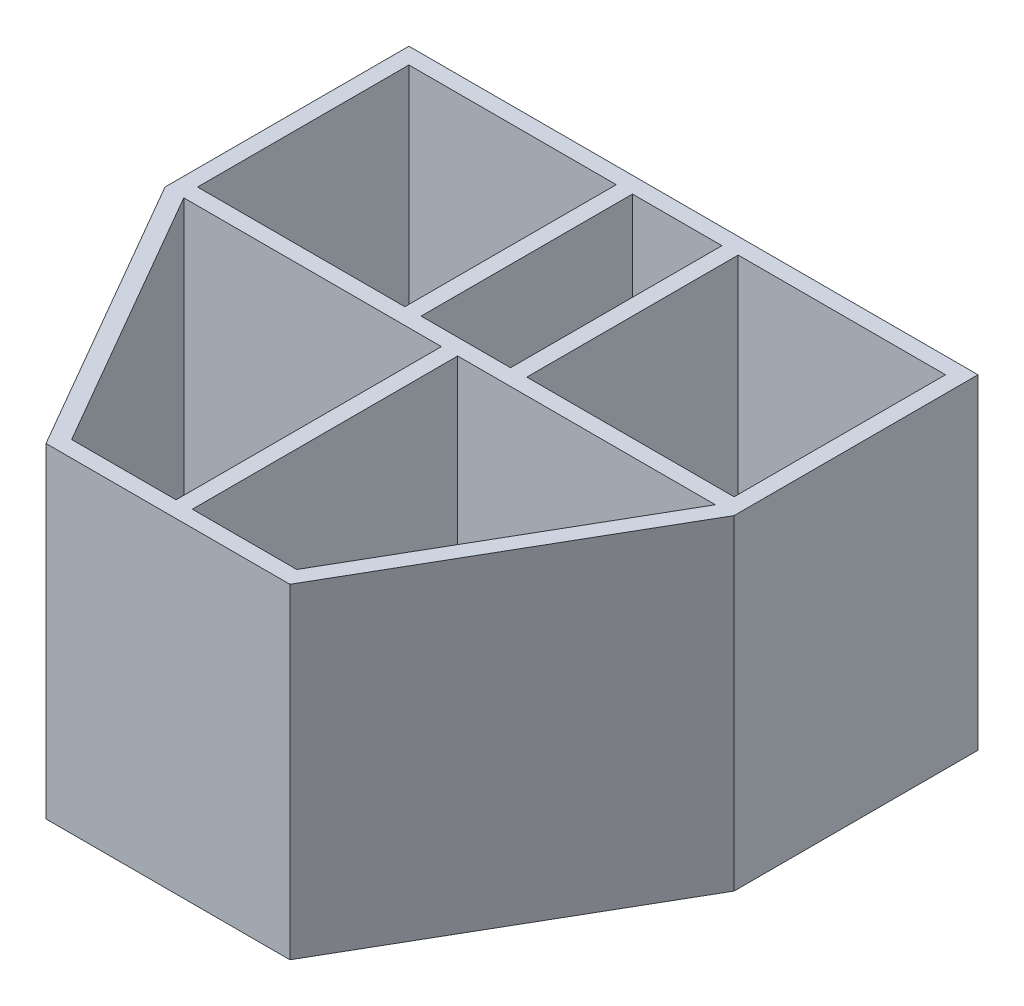
SolidWorks part; units mm, degrees
ref_plane "前视基准面" through (0, 0, 0) normal (0, 0, 1) x (1, 0, 0)
ref_plane "上视基准面" through (0, 0, 0) normal (0, 1, 0) x (1, 0, 0)
ref_plane "右视基准面" through (0, 0, 0) normal (1, 0, 0) x (0, 0, -1)
ref_plane "InnerBottom" through (0, 0, 0) normal (0, 1, 0) x (1, 0, 0)
sketch "Circle" plane through (0, 0, 0) normal (0, 1, 0) x (1, 0, 0)
  line L0 (0, 0) -> (0, 200) construction
  dimension "R" = 200
ref_plane "InnerTop" through (0, 60, 0) normal (0, 1, 0) x (1, 0, 0)
ref_plane "SlotCenterV" through (0, 0, 0) normal (1, 0, 0) x (0, 0, -1)
ref_plane "SlotCenterH" through (0, 0, 0) normal (0, 0, 1) x (1, 0, 0)
ref_axis "CenterAxis" through (0, 0, -200) along (0, 1, 0)
sketch "STwoSlot" [suppressed] plane through (0, 0, 0) normal (0, 1, 0) x (1, 0, 0)
  line L0 (-32.1742, 0) -> (29.2905, 0) construction
  line L1 (0, 21.3687) -> (0, -19.6077) construction
  line L2 (-5, 4) -> (-5, -4)
  line L3 (-5, -4) -> (-7, -4)
  line L4 (-7, -4) -> (-7, -3)
  line L5 (-7, -3) -> (-10, -3)
  line L6 (-10, 3) -> (-7, 3)
  line L7 (-7, 3) -> (-7, 4)
  line L8 (-7, 4) -> (-5, 4)
  line L9 (5, -4) -> (7, -4)
  line L10 (7, -4) -> (7, -3)
  line L11 (7, -3) -> (10, -3)
  line L12 (10, 3) -> (7, 3)
  line L13 (7, 3) -> (7, 4)
  line L14 (7, 4) -> (5, 4)
  line L15 (5, 4) -> (5, -4)
  arc A0 (-10, -3) -> (-10, 3) centre (-10, 0) cw
  arc A1 (10, -3) -> (10, 3) centre (10, 0) ccw
  dimension "D4" = 3
  dimension "D1" = 8
  dimension "D2" = 2
  dimension "D3" = 3
  dimension "D5" = 10
sketch "STwoBase" [suppressed] plane through (0, 0, 0) normal (0, 1, 0) x (1, 0, 0)
  line L0 (0, 7.5) -> (0, -6.5) construction
  line L1 (-17.5, -7.5) -> (17.5, -7.5)
  line L2 (-17.5, -7.5) -> (-17.5, 7.5)
  line L3 (-17.5, 7.5) -> (17.5, 7.5)
  line L4 (17.5, -7.5) -> (17.5, 7.5)
  line L5 (-17.5, -7.5) -> (17.5, 7.5) construction
  line L6 (-17.5, 7.5) -> (17.5, -7.5) construction
  line L7 (-16.5, -6.5) -> (-0.5, -6.5)
  line L8 (-16.5, -6.5) -> (-16.5, 6.5)
  line L9 (-16.5, 6.5) -> (-0.5, 6.5)
  line L10 (16.5, -6.5) -> (16.5, 6.5)
  line L11 (-16.5, -6.5) -> (16.5, 6.5) construction
  line L12 (-16.5, 6.5) -> (16.5, -6.5) construction
  line L13 (-0.5, 6.5) -> (-0.5, -6.5)
  line L14 (0.5, 6.5) -> (0.5, -6.5)
  line L15 (0.5, 6.5) -> (16.5, 6.5)
  line L16 (0.5, -6.5) -> (16.5, -6.5)
  line L17 (0, 6.5) -> (0, -6.5) construction
  point P0 (0, 0)
  point P6 (0, 0)
  dimension "D1" = 35
  dimension "D5" = 1
  dimension "D2" = 15
  dimension "D3" = 1
  dimension "D4" = 1
extrude "FTwoBase" [suppressed] add sketch "STwoBase" along normal blind 20
sketch "SFiveSlotTP1" plane through (0, 0, 0) normal (0, 1, 0) x (1, 0, 0)
  line L0 (0, 21.9383) -> (0, -21.3523) construction
  line L1 (-37.6162, 0) -> (47.1378, 0) construction
  line L2 (-5.15, 11) -> (-5.15, 3)
  line L3 (-5.15, 3) -> (-7.55, 3)
  line L4 (-7.55, 3) -> (-7.55, 4)
  line L5 (-7.55, 4) -> (-10.55, 4)
  line L6 (-10.55, 10) -> (-7.55, 10)
  line L7 (-7.55, 10) -> (-7.55, 11)
  line L8 (-7.55, 11) -> (-5.15, 11)
  line L9 (-10.55, 7) -> (-5.15, 7) construction
  line L10 (7.55, 10) -> (7.55, 11)
  line L11 (10.55, 10) -> (7.55, 10)
  line L12 (7.55, 4) -> (10.55, 4)
  line L13 (7.55, 3) -> (7.55, 4)
  line L14 (5.15, 3) -> (7.55, 3)
  line L15 (5.15, 11) -> (5.15, 3)
  line L16 (7.55, 11) -> (5.15, 11)
  line L17 (-1.2, 7) -> (1.2, 7) construction
  line L18 (-1.2, 11.5) -> (1.2, 11.5)
  line L19 (-1.2, 11.5) -> (-1.2, 2.5)
  line L20 (-1.2, 2.5) -> (1.2, 2.5)
  line L21 (1.2, 11.5) -> (1.2, 2.5)
  line L22 (-7.2169, -4.1) -> (-2.7169, -11.8942)
  line L23 (-2.7169, -11.8942) -> (-4.7953, -13.0942)
  line L24 (-4.7953, -13.0942) -> (-9.2953, -5.3)
  line L25 (-9.2953, -5.3) -> (-7.2169, -4.1)
  line L26 (2.7169, -11.8942) -> (4.7953, -13.0942)
  line L27 (7.2169, -4.1) -> (2.7169, -11.8942)
  line L28 (4.7953, -13.0942) -> (9.2953, -5.3)
  line L29 (9.2953, -5.3) -> (7.2169, -4.1)
  line L30 (-8.2561, -4.7) -> (-3.7561, -12.4942) construction
  line L31 (-6.35, 11) -> (-6.35, 3) construction
  line L32 (6.35, 11) -> (6.35, 3) construction
  arc A0 (-10.55, 4) -> (-10.55, 10) centre (-10.55, 7) cw
  arc A1 (10.55, 4) -> (10.55, 10) centre (10.55, 7) ccw
  dimension "D4" = 3
  dimension "D1" = 8
  dimension "T3" = 2.4
  dimension "D3" = 3
  dimension "B1" = 9
  dimension "T1" = 2.4
  dimension "D7" = 7
  dimension "T2" = 2.4
  dimension "B2" = 9
  dimension "D12" = 60
  dimension "A" = 11.1
  dimension "F" = 9.5
  dimension "F2" = 12.7
sketch "SFiveBaseTP1" plane through (0, 0, 0) normal (0, 1, 0) x (1, 0, 0)
  line L0 (0, 29.2892) -> (0, -26.2802) construction
  line L1 (-17.5, 15) -> (17.5, 15)
  line L2 (17.5, 15) -> (17.5, 0)
  line L3 (17.5, 0) -> (7.5, -17.3205)
  line L4 (7.5, -17.3205) -> (-7.5, -17.3205)
  line L5 (-7.5, -17.3205) -> (-17.5, 0)
  line L6 (-17.5, 0) -> (-17.5, 15)
  line L8 (-16.3453, 0) -> (-6.9226, -16.3205)
  line L9 (-16.5, 14) -> (-3.75, 14)
  line L10 (-16.5, 14) -> (-16.5, 1)
  line L11 (-16.5, 1) -> (-3.75, 1)
  line L12 (16.5, 14) -> (16.5, 1)
  line L13 (-6.9226, -16.3205) -> (-0.5, -16.3205)
  line L14 (-0.5, -16.3205) -> (-0.5, 0)
  line L15 (-0.5, 0) -> (-16.3453, 0)
  line L16 (0.5, 0) -> (0.5, -16.3205)
  line L17 (0.5, -16.3205) -> (6.9226, -16.3205)
  line L18 (6.9226, -16.3205) -> (16.3453, 0)
  line L19 (16.3453, 0) -> (0.5, 0)
  line L20 (-3.75, 14) -> (-3.75, 1)
  line L21 (-2.75, 14) -> (-2.75, 1)
  line L22 (2.75, 14) -> (2.75, 1)
  line L23 (3.75, 14) -> (3.75, 1)
  line L24 (-2.75, 14) -> (2.75, 14)
  line L25 (3.75, 14) -> (16.5, 14)
  line L26 (-2.75, 1) -> (2.75, 1)
  line L27 (3.75, 1) -> (16.5, 1)
  dimension "D1" = 35
  dimension "D2" = 60
  dimension "D3" = 15
  dimension "D4" = 15
  dimension "D5" = 1
  dimension "D6" = 1
  dimension "D7" = 1
  dimension "D8" = 1
  dimension "D9" = 1
  dimension "D10" = 1
  dimension "D11" = 13
  dimension "D12" = 1
  dimension "D13" = 1
  dimension "D14" = 1
  dimension "D15" = 1
  dimension "D16" = 7.5
extrude "FFiveBaseTP1" add sketch "SFiveBaseTP1" along normal blind 20
sketch "SThreeSlot" [suppressed] plane through (0, 0, 0) normal (0, 1, 0) x (1, 0, 0)
  line L0 (-38.3697, 0) -> (49.7492, 0) construction
  line L1 (0, 31.5127) -> (0, -28.5949) construction
  line L2 (-9.2953, -5.3) -> (-4.7953, -13.0942)
  line L3 (-1.2, 11.5) -> (1.2, 11.5)
  line L4 (-1.2, 11.5) -> (-1.2, 2.5)
  line L5 (-1.2, 2.5) -> (1.2, 2.5)
  line L6 (1.2, 11.5) -> (1.2, 2.5)
  line L7 (-9.2953, -5.3) -> (-7.2169, -4.1)
  line L8 (-4.7953, -13.0942) -> (-2.7169, -11.8942)
  line L9 (-7.2169, -4.1) -> (-2.7169, -11.8942)
  line L10 (2.7169, -11.8942) -> (7.2169, -4.1)
  line L11 (2.7169, -11.8942) -> (4.7953, -13.0942)
  line L12 (7.2169, -4.1) -> (9.2953, -5.3)
  line L13 (4.7953, -13.0942) -> (9.2953, -5.3)
  line L14 (-1.2, 7) -> (1.2, 7) construction
  line L15 (-8.2561, -4.7) -> (-3.7561, -12.4942) construction
  dimension "B1" = 9
  dimension "T1" = 2.4
  dimension "T2" = 2.4
  dimension "B2" = 9
  dimension "F" = 9.5
  dimension "D1" = 60
  dimension "D2" = 11.1
  dimension "D3" = 7
sketch "SThreeBase" [suppressed] plane through (0, 0, 0) normal (0, 1, 0) x (1, 0, 0)
  line L0 (-19.047, 0) -> (-7.5, -20)
  line L1 (-7.5, -20) -> (7.5, -20)
  line L2 (7.5, -20) -> (19.047, 0)
  line L3 (19.047, 0) -> (5, 0)
  line L4 (5, 0) -> (5, 15)
  line L5 (5, 15) -> (-5, 15)
  line L6 (-5, 15) -> (-5, 0)
  line L7 (-19.047, 0) -> (-5, 0)
  line L8 (0, 24.0859) -> (0, -25.4306) construction
  line L9 (0, 31.5127) -> (0, -28.5949) construction
  line L11 (4, 0) -> (4, 14)
  line L12 (4, 14) -> (-4, 14)
  line L13 (-4, 14) -> (-4, 0)
  line L14 (-17.315, -1) -> (-4, -1)
  line L15 (-17.315, -1) -> (-6.9226, -19)
  line L16 (-6.9226, -19) -> (-0.5, -19)
  line L17 (6.9226, -19) -> (17.315, -1)
  line L18 (17.315, -1) -> (4, -1)
  line L19 (-4, -1) -> (-0.5, -1)
  line L20 (-4, 0) -> (4, 0)
  line L21 (-0.5, -1) -> (-0.5, -19)
  line L22 (-4, 14) -> (-4, -1) construction
  line L23 (4, -1) -> (4, 14) construction
  line L24 (0.5, -1) -> (0.5, -19)
  line L25 (0.5, -1) -> (4, -1)
  line L26 (0.5, -19) -> (6.9226, -19)
  line L28 (-6.9226, -19) -> (6.9226, -19) construction
  dimension "D3" = 15
  dimension "D6" = 1
  dimension "D7" = 1
  dimension "D2" = 15
  dimension "D1" = 10
  dimension "D4" = 20
  dimension "D5" = 60
extrude "FThreeBase" [suppressed] add sketch "SThreeBase" along normal blind 20
sketch "SUsbSlot" [suppressed] plane through (0, 0, 0) normal (0, 1, 0) x (1, 0, 0)
  line L0 (0, 4.2432) -> (0, -4.6578) construction
  line L2 (-2.5, -6) -> (2.5, -6)
  line L3 (-2.5, -6) -> (-2.5, 6)
  line L4 (-2.5, 6) -> (2.5, 6)
  line L5 (2.5, -6) -> (2.5, 6)
  line L6 (-2.5, -6) -> (2.5, 6) construction
  line L7 (-2.5, 6) -> (2.5, -6) construction
  point P3 (0, 0)
  dimension "UsbL" = 12
  dimension "UsbKd" = 5
sketch "SUsbBase" [suppressed] plane through (0, 0, 0) normal (0, 1, 0) x (1, 0, 0)
  line L1 (-5, -9) -> (5, -9)
  line L2 (-5, -9) -> (-5, 9)
  line L3 (-5, 9) -> (5, 9)
  line L4 (5, -9) -> (5, 9)
  line L5 (-5, -9) -> (5, 9) construction
  line L6 (-5, 9) -> (5, -9) construction
  line L7 (-4, 8) -> (4, 8)
  line L8 (4, -8) -> (4, 8)
  line L9 (-4, -8) -> (4, -8)
  line L10 (-4, -8) -> (-4, 8)
  dimension "D1" = 10
  dimension "D2" = 18
extrude "FUsbBase" [suppressed] add sketch "SUsbBase" along normal blind 20
equation "\"SlotL\"= 9"
equation "\"SlotKD\"= 2.4"
equation "\"B1@SFiveSlotTP1\"=\"SlotL\""
equation "\"B2@SFiveSlotTP1\"=\"SlotL\""
equation "\"T1@SFiveSlotTP1\"=\"SlotKD\""
equation "\"T3@SFiveSlotTP1\"=\"SlotKD\""
equation "\"T2@SFiveSlotTP1\"=\"SlotKD\""
equation "\"T1@SThreeSlot\"=\"SlotKD\""
equation "\"T2@SThreeSlot\"=\"SlotKD\""
equation "\"B1@SThreeSlot\"=\"SlotL\""
equation "\"B2@SThreeSlot\"=\"SlotL\""
equation "\"BaseTn\"=1"
equation "\"D5@SFiveBaseTP1\"=\"BaseTn\""
equation "\"D6@SFiveBaseTP1\"=\"BaseTn\""
equation "\"D7@SFiveBaseTP1\"=\"BaseTn\""
equation "\"D8@SFiveBaseTP1\"=\"BaseTn\""
equation "\"D9@SFiveBaseTP1\"=\"BaseTn\""
equation "\"D10@SFiveBaseTP1\"=\"BaseTn\""
equation "\"D12@SFiveBaseTP1\"=\"BaseTn\""
equation "\"D13@SFiveBaseTP1\"=\"BaseTn\""
equation "\"D5@STwoBase\"=\"BaseTn\""
equation "\"D3@STwoBase\"=\"BaseTn\""
equation "\"D4@STwoBase\"=\"BaseTn\""
equation "\"BaseH\"= 20"
equation "\"D1@FTwoBase\"=\"BaseH\""
equation "\"D1@FFiveBaseTP1\"=\"BaseH\""
equation "\"D6@SThreeBase\"=\"BaseTn\""
equation "\"D1@FThreeBase\"=\"BaseH\""
equation "\"D7@SThreeBase\"=\"BaseTn\""
equation "\"D3@SUsbBase\"=\"BaseTn\""
equation "\"D1@FUsbBase\"=\"BaseH\""
equation "\"D14@SFiveBaseTP1\"=\"BaseTn\""
equation "\"D15@SFiveBaseTP1\"=\"BaseTn\""
